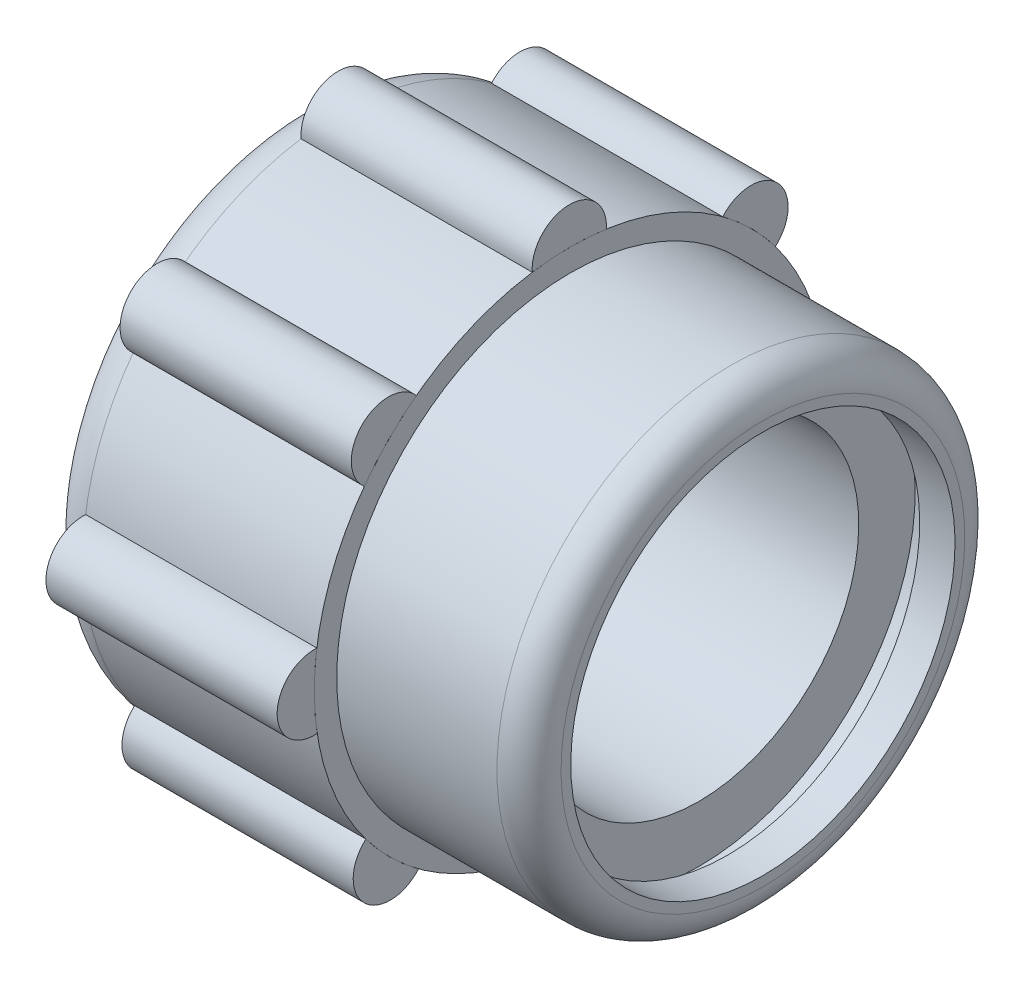
SolidWorks part; units mm, degrees
material "PBT Общее назначение"
ref_plane "Спереди" through (0, 0, 0) normal (0, 0, 1) x (1, 0, 0)
ref_plane "Сверху" through (0, 0, 0) normal (0, 1, 0) x (1, 0, 0)
ref_plane "Справа" through (0, 0, 0) normal (1, 0, 0) x (0, 0, -1)
sketch "Эскиз2" plane through (0, 0, 0) normal (0, 0, 1) x (1, 0, 0)
  line L0 (0, 6.8983) -> (0, 8)
  line L1 (0, 8) -> (8.5, 8)
  line L2 (8.5, 8) -> (8.5, 7.3)
  line L3 (8.5, 7.3) -> (14.5, 7.3)
  line L4 (14.5, 7.3) -> (14.5, 6.2654)
  line L5 (14.5, 6.2654) -> (16.5, 6.2654)
  line L6 (16.5, 6.2654) -> (16.5, 3)
  line L7 (16.5, 3) -> (12.5, 3)
  line L8 (12.5, 3) -> (12.5, 4.991)
  line L9 (12.5, 4.991) -> (0.7, 4.991)
  line L12 (0, 0) -> (0, 6.8983) construction
  line L13 (0, 6.8983) -> (0.7, 6.8983)
  line L16 (0.7, 6.8983) -> (0.7, 4.991)
  line L17 (0, 0) -> (18.5797, 0) construction
  line L18 (12.5, 4.991) -> (12.5, 6.751)
  line L19 (12.5, 6.751) -> (13.3974, 6.751)
  line L20 (13.3974, 6.751) -> (13.3974, 5.9957)
  line L21 (13.3974, 5.9957) -> (14.5, 5.9957)
  line L22 (14.5, 5.9957) -> (14.5, 6.2654)
  line L23 (14.5, 5.9957) -> (14.5, 6.2654)
  dimension "D1" = 16.5
  dimension "D2" = 8
  dimension "D3" = 4.991
  dimension "D4" = 3
  dimension "D5" = 0.7
  dimension "D6" = 8.5
  dimension "D7" = 6
  dimension "D8" = 3.2654
  dimension "D9" = 1.76
  dimension "D10" = 4
  dimension "D11" = 0.7
  dimension "D12" = 1.9074
  dimension "D13" = 0.8974
  dimension "D14" = 0.7553
revolve "Повернуть1" add sketch "Эскиз2" angle 360 about L17 region at (6.5423, 6.4385, 0)
fillet "Скругление3" radius 1.3 1 edges at (0, -8, 0)
fillet "Скругление4" radius 1 1 edges at (14.5, -7.3, 0)
ref_plane "Плоскость5" through (1.2848, 0, 0) normal (1, 0, 0) x (0, 0, -1)
sketch "Эскиз5" plane through (1.2848, 0, 0) normal (1, 0, 0) x (0, 0, -1)
  arc A0 (7.9141, -1.114) -> (7.9099, 1.1972) centre (7.9999, 0.0417) ccw
  circle A1 centre (0, 0) radius 8 construction
  spline S0 degree 3 poles (7.9141, -1.114) (8.0354, -0.393) (8.023, 0.4766) (7.9099, 1.1972) knots 0 0 0 0 0.218344 0.218344 0.218344 0.218344
  point P4 (7.9141, -1.114)
  point P5 (7.9099, 1.1972)
  dimension "D1" = 2.3204
  dimension "D2" = 1.159
extrude "Бобышка-Вытянуть5" add sketch "Эскиз5" along normal up to surface (7.2152 mm away) separate body up to face at (8.5, -7.3, 0)
pattern_circular "Круговой массив2" count 8 over 360 about axis through (1.2848, 0, 0) along (1, 0, 0) of bodies 102
